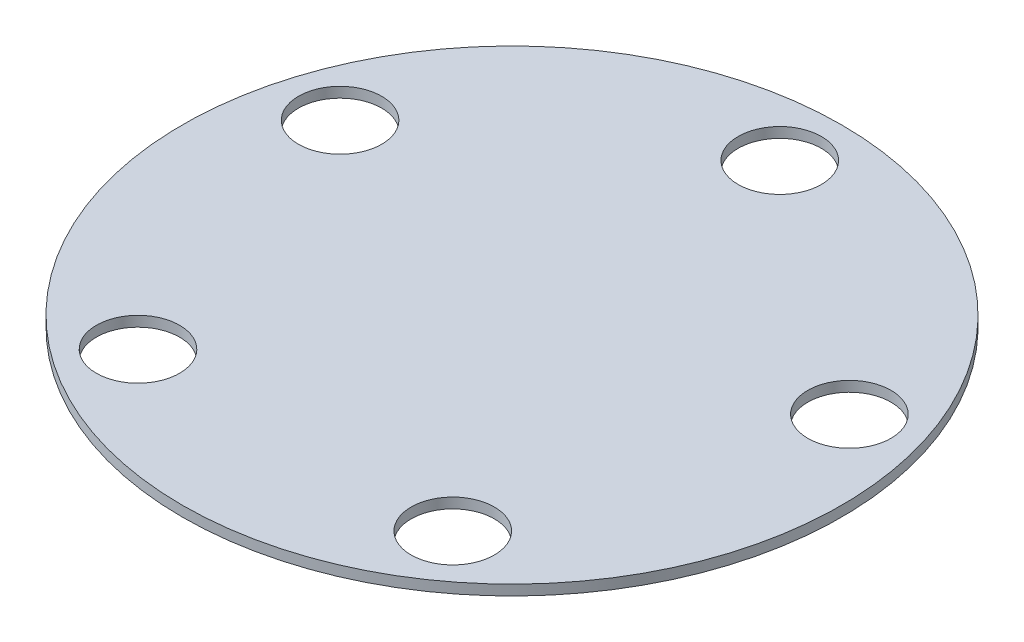
SolidWorks part; units mm, degrees
material "6061 Alloy"
ref_plane "Front Plane" through (0, 0, 0) normal (0, 0, 1) x (1, 0, 0)
ref_plane "Top Plane" through (0, 0, 0) normal (0, 1, 0) x (1, 0, 0)
ref_plane "Right Plane" through (0, 0, 0) normal (1, 0, 0) x (0, 0, -1)
sketch "Sketch1" plane through (0, 0, 0) normal (0, 1, 0) x (1, 0, 0)
  circle A0 centre (0, 0) radius 101.6
  dimension "D1" = 203.2
extrude "Boss-Extrude1" add sketch "Sketch1" along normal blind 3.175
sketch "Sketch2" plane through (0, 3.175, 0) normal (0, 1, 0) x (1, 0, 0)
  circle A0 centre (0, 82.55) radius 12.827
  circle A1 centre (78.5097, 25.5094) radius 12.827
  circle A2 centre (48.5217, -66.7844) radius 12.827
  circle A3 centre (-48.5217, -66.7844) radius 12.827
  circle A4 centre (-78.5097, 25.5094) radius 12.827
  point P12 (0, 0)
  dimension "D1" = 25.654
  dimension "D3" = 82.55
  dimension "D2" = 5
extrude "Cut-Extrude1" cut sketch "Sketch2" against normal blind 3.175
